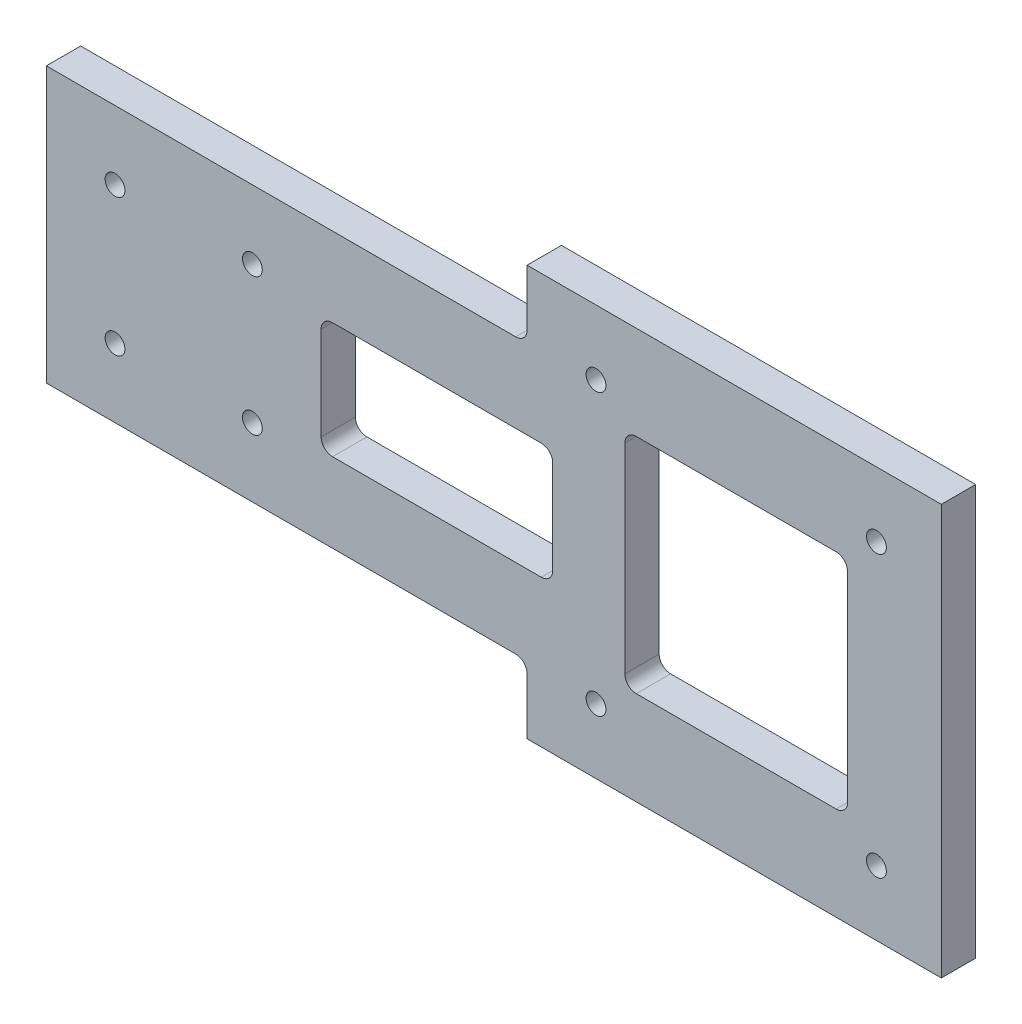
SolidWorks part; units mm, degrees
material "6061-T6 (SS)"
ref_plane "Front" through (0, 0, 0) normal (0, 0, 1) x (1, 0, 0)
ref_plane "Top" through (0, 0, 0) normal (0, 1, 0) x (1, 0, 0)
ref_plane "Right" through (0, 0, 0) normal (1, 0, 0) x (0, 0, -1)
sketch "Sketch1" plane through (0, 0, 0) normal (0, 0, 1) x (1, 0, 0)
  line L0 (95.25, 38.1) -> (95.25, 56.8909)
  line L1 (95.25, 38.1) -> (-38.1, 38.1)
  line L3 (95.25, -38.1) -> (-38.1, -38.1)
  line L4 (-38.1, 38.1) -> (-38.1, -38.1)
  line L5 (-38.1, -38.1) -> (0, 0) construction
  line L6 (0, 0) -> (-38.1, 38.1) construction
  line L7 (95.25, 56.8909) -> (210.1409, 56.8909)
  line L8 (210.1409, 56.8909) -> (210.1409, 30.8909)
  line L9 (210.1409, 30.8909) -> (122.3591, 30.8909)
  line L10 (122.3591, 30.8909) -> (122.3591, -30.8909)
  line L11 (122.3591, -30.8909) -> (210.1409, -30.8909)
  line L12 (210.1409, -30.8909) -> (210.1409, -56.8909)
  line L13 (210.1409, -56.8909) -> (95.25, -56.8909)
  line L14 (95.25, -56.8909) -> (95.25, -38.1)
  line L15 (192.1409, -30.8909) -> (192.1409, -38.8909) construction
  line L16 (192.1409, -38.8909) -> (192.1409, -56.8909) construction
  line L17 (0, 0) -> (153.25, 0) construction
  line L18 (192.1409, -38.8909) -> (114.3591, 38.8909) construction
  line L19 (192.1409, 38.8909) -> (114.3591, -38.8909) construction
  line L20 (122.3591, 30.8909) -> (153.25, 0) construction
  line L21 (153.25, 0) -> (122.3591, -30.8909) construction
  line L22 (192.1409, 38.8909) -> (192.1409, 56.8909) construction
  line L23 (192.1409, 38.8909) -> (210.1409, 38.8909) construction
  line L24 (192.1409, 38.8909) -> (192.1409, 30.8909) construction
  line L25 (114.3591, 38.8909) -> (95.25, 38.8909) construction
  line L26 (0, 0) -> (122.3591, 0) construction
  line L27 (0, 0) -> (95.25, -38.1) construction
  line L28 (0, 0) -> (95.25, 38.1) construction
  line L29 (192.1409, -38.8909) -> (210.1409, -38.8909) construction
  line L30 (153.25, 0) -> (153.25, 30.8909) construction
  line L31 (153.25, 0) -> (122.3591, 0) construction
  circle A0 centre (153.25, 0) radius 55 construction
  point P0 (0, 0)
  point P17 (192.1409, 38.8909)
  point P18 (192.1409, -38.8909)
  point P19 (114.3591, 38.8909)
  point P20 (114.3591, -38.8909)
  dimension "D2" = 110
  dimension "D1" = 76.2
  dimension "D3" = 90
  dimension "D5" = 8
  dimension "D6" = 18
  dimension "D7" = 133.35
  dimension "D9" = 58
  dimension "D10" = 0
extrude "Boss-Extrude1" add sketch "Sketch1" along normal blind 9.525
hole_wizard "M5 Clearance Hole1" positions "Sketch3" profile "Sketch4" hole size "M5" standard "ANSI Metric"
sketch "Sketch3" plane through (0, 0, 9.525) normal (0, 0, 1) x (1, 0, 0)
  line L0 (0, 0) -> (153.25, 0) construction
  line L2 (192.1409, -38.8909) -> (114.3591, 38.8909) construction
  line L4 (192.1409, 38.8909) -> (114.3591, -38.8909) construction
  line L6 (122.3591, 30.8909) -> (153.25, 0) construction
  line L7 (153.25, 0) -> (122.3591, -30.8909) construction
  line L8 (95.25, 38.1) -> (-38.1, 38.1) construction
  line L12 (95.25, -38.1) -> (95.25, -56.8909) construction
  circle A0 centre (153.25, 0) radius 55 construction
  point P0 (192.1409, 38.8909)
  point P2 (192.1409, -38.8909)
  point P4 (114.3591, 38.8909)
  point P6 (114.3591, -38.8909)
  dimension "D1" = 110
  dimension "D2" = 135
  dimension "D3" = 90
  dimension "D4" = 58
sketch "Sketch4" plane through (192.1409, 38.8909, 9.525) normal (1, 0, 0) x (0, -1, 0)
  line L0 (0, 0) -> (0, 20.4024)
  line L1 (0, 20.4024) -> (2.75, 18.75)
  line L2 (2.75, 18.75) -> (2.75, 0)
  line L5 (2.75, 0) -> (0, 0)
  line L10 (0, 20.4024) -> (-2.75, 18.75) construction
  line L11 (0, -6.35) -> (0, 107.95) construction
  dimension "Hole Dia." = 5.5
  dimension "Hole Depth" = 18.75
  dimension "Drill Angle" = 118
fillet "Fillet1" radius 3.175 4 edges at (122.3591, 30.8909, 4.7625) (122.3591, -30.8909, 4.7625) (95.25, -38.1, 4.7625) (95.25, 38.1, 4.7625)
hole_wizard "M5 Clearance Hole2" positions "Sketch5" profile "Sketch6" hole size "M5" standard "ANSI Metric"
sketch "Sketch5" plane through (0, 0, 9.525) normal (0, 0, 1) x (1, 0, 0)
  line L0 (-19.05, 19.05) -> (19.05, 19.05) construction
  line L1 (19.05, 19.05) -> (19.05, -19.05) construction
  line L2 (19.05, -19.05) -> (-19.05, -19.05) construction
  line L3 (-19.05, -19.05) -> (-19.05, 19.05) construction
  line L5 (92.075, 38.1) -> (-38.1, 38.1) construction
  line L9 (-38.1, -38.1) -> (-19.05, -19.05) construction
  line L11 (-19.05, 19.05) -> (-38.1, 38.1) construction
  point P0 (-19.05, 19.05)
  point P2 (19.05, 19.05)
  point P4 (19.05, -19.05)
  point P6 (-19.05, -19.05)
  dimension "D1" = 19.05
  dimension "D2" = 38.1
sketch "Sketch6" plane through (-19.05, 19.05, 9.525) normal (1, 0, 0) x (0, -1, 0)
  line L0 (0, 0) -> (0, 20.4024)
  line L1 (0, 20.4024) -> (2.75, 18.75)
  line L2 (2.75, 18.75) -> (2.75, 0)
  line L5 (2.75, 0) -> (0, 0)
  line L10 (0, 20.4024) -> (-2.75, 18.75) construction
  line L11 (0, -6.35) -> (0, 107.95) construction
  dimension "Hole Dia." = 5.5
  dimension "Hole Depth" = 18.75
  dimension "Drill Angle" = 118
sketch "Sketch7" plane through (0, 0, 9.525) normal (0, 0, 1) x (1, 0, 0)
  line L0 (19.05, 19.05) -> (19.05, 38.1) construction
  line L1 (102.3591, -16.1) -> (38.1, -16.1)
  line L2 (102.3591, -16.1) -> (102.3591, 16.1)
  line L3 (102.3591, 16.1) -> (38.1, 16.1)
  line L4 (38.1, -16.1) -> (38.1, 16.1)
  line L5 (102.3591, -16.1) -> (38.1, 16.1) construction
  line L6 (102.3591, 16.1) -> (38.1, -16.1) construction
  line L7 (122.3591, -27.7159) -> (122.3591, 27.7159) construction
  line L8 (92.075, 38.1) -> (-38.1, 38.1) construction
  line L9 (0, 0) -> (70.2296, 0) construction
  line L10 (19.05, 19.05) -> (38.1, 19.05) construction
  point P0 (70.2296, 0)
  dimension "D1" = 20
  dimension "D2" = 22
extrude "Cut-Extrude1" cut sketch "Sketch7" against normal through all
fillet "Fillet2" radius 3.175 4 edges at (102.3591, -16.1, 4.7625) (102.3591, 16.1, 4.7625) (38.1, 16.1, 4.7625) (38.1, -16.1, 4.7625)
sketch "Sketch8" plane through (0, 0, 9.525) normal (0, 0, 1) x (1, 0, 0)
  line L0 (125.5341, 30.8909) -> (210.1409, 30.8909) construction
  line L1 (210.1409, -30.8909) -> (184.1409, -30.8909)
  line L2 (210.1409, -30.8909) -> (210.1409, 30.8909)
  line L3 (210.1409, 30.8909) -> (184.1409, 30.8909)
  line L4 (184.1409, -30.8909) -> (184.1409, 30.8909)
  line L5 (210.1409, -56.8909) -> (210.1409, -30.8909) construction
extrude "Boss-Extrude2" add sketch "Sketch8" against normal up to surface (9.525 mm away) up to face at (70.2296, 0, 0)
fillet "Fillet3" radius 3.175 2 edges at (184.1409, -30.8909, 4.7625) (184.1409, 30.8909, 4.7625)
